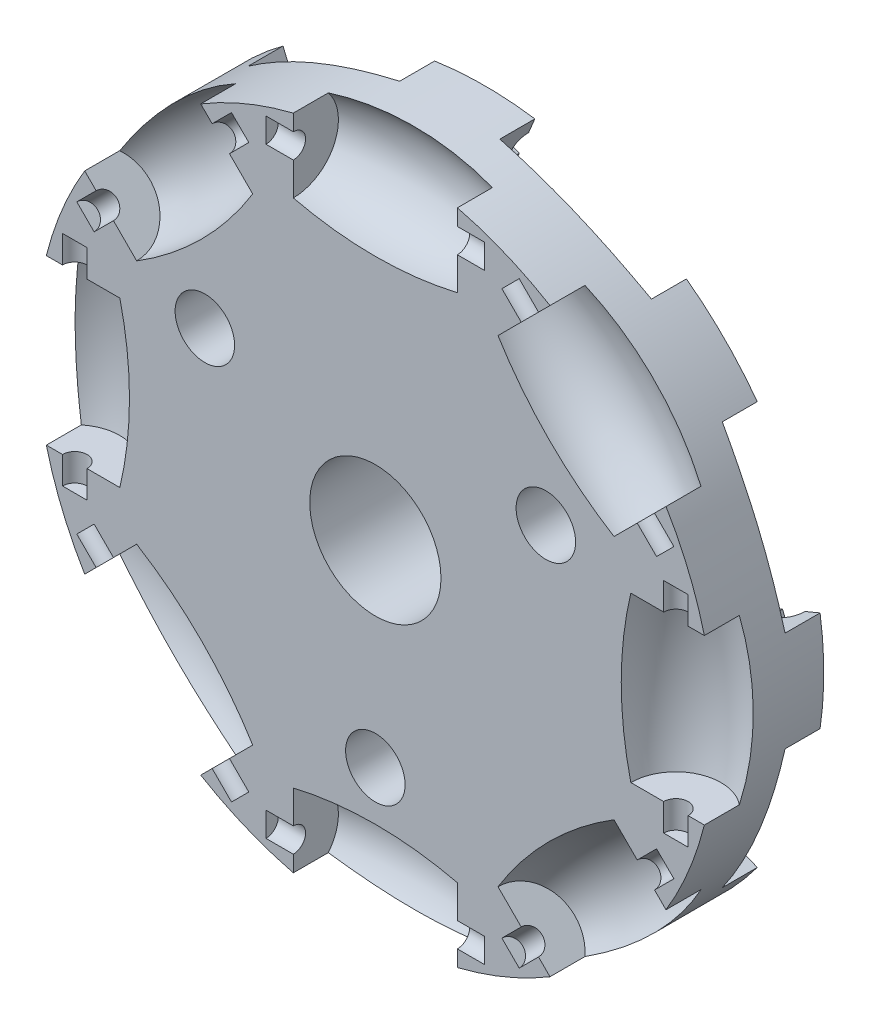
SolidWorks part; units mm, degrees
ref_plane "Front Plane" through (0, 0, 0) normal (0, 0, 1) x (1, 0, 0)
ref_plane "Top Plane" through (0, 0, 0) normal (0, 1, 0) x (1, 0, 0)
ref_plane "Right Plane" through (0, 0, 0) normal (1, 0, 0) x (0, 0, -1)
sketch "Sketch1" plane through (0, 0, 0) normal (0, 0, 1) x (1, 0, 0)
  circle A0 centre (0, 0) radius 24.6062
  point P11 (0, 0)
  dimension "D1" = 49.2125
extrude "Boss-Extrude1" add sketch "Sketch1" along normal mid plane 7.9375
ref_plane "Plane1" through (0, 0, 3.9688) normal (0, 0, 1) x (1, 0, 0)
ref_plane "Plane2" through (0, 0, -3.9688) normal (0, 0, 1) x (1, 0, 0)
sketch "Sketch5" plane through (0, 0, 3.9688) normal (0, 0, 1) x (1, 0, 0)
  line L0 (-5.9531, 25.0843) -> (-5.9531, 21.8122)
  line L1 (-5.9531, 21.8122) -> (5.9531, 21.8122)
  line L2 (5.9531, 21.8122) -> (5.9531, 25.0843)
  line L3 (-5.9531, 21.8122) -> (-8.0326, 21.8122) construction
  arc A2 (-5.9531, 25.0843) -> (5.9531, 25.0843) centre (0, 0) cw
  point P2 (0, 25.781)
  point P7 (0, 21.8122)
  dimension "D1" = 11.9062
  dimension "D2" = 7.9375
  dimension "D3" = 21.8122
revolve "Cut-Revolve5" cut sketch "Sketch5" angle 360 about L1
sketch "Sketch8" plane through (0, 0, -3.9688) normal (0, 0, 1) x (1, 0, 0)
  line L0 (4.0994, 25.453) -> (2.8472, 22.4301)
  line L1 (2.8472, 22.4301) -> (13.8472, 17.8737)
  line L2 (13.8472, 17.8737) -> (15.0993, 20.8967)
  line L3 (2.8472, 22.4301) -> (-2.3537, 24.5843) construction
  line L4 (0, 0) -> (9.4164, 22.7332) construction
  line L5 (0, 0) -> (0, 7.8748) construction
  arc A0 (4.0994, 25.453) -> (15.0993, 20.8967) centre (0, 0) cw
  arc A2 (-5.9531, 23.8753) -> (5.9531, 23.8753) centre (0, 0) ccw construction
  point P6 (8.3472, 20.1519)
  point P14 (9.866, 23.8185)
  dimension "D1" = 11.9062
  dimension "D2" = 7.9375
  dimension "D3" = 22.5
  dimension "D4" = 21.8122
revolve "Cut-Revolve6" cut sketch "Sketch8" angle 360 about L3
sketch "Sketch6" plane through (0, 0, 0) normal (1, 0, 0) x (0, 0, -1)
  arc A0 (-3.9688, 18.5402) -> (-1.429, 23.8753) centre (-3.9688, 21.8122) ccw construction
  circle A1 centre (-3.9688, 21.8122) radius 0.889
  point P4 (-3.9688, 21.8122)
  dimension "D1" = 1.778
extrude "Cut-Extrude2" cut sketch "Sketch6" against normal mid plane 15.875
ref_axis "Axis1" through (0, 0, -8.8615) along (0, 0, 1)
ref_plane "Plane3" through (0, 0, 0) normal (0.9239, -0.3827, 0) x (0, 0, -1)
sketch "Sketch10" plane through (0, 0, 0) normal (0.9239, -0.3827, 0) x (0, 0, -1)
  arc A1 (1.429, 23.8753) -> (3.9688, 18.5402) centre (3.9688, 21.8123) ccw construction
  circle A2 centre (3.9688, 21.8123) radius 0.889
  point P4 (3.9688, 21.8123)
  dimension "D1" = 1.778
extrude "Cut-Extrude3" cut sketch "Sketch10" against normal mid plane 15.875
pattern_circular "CirPattern1" count 8 over 360 about axis through (0, 0, 3.9688) along (0, 0, -1) of "Cut-Revolve5", "Cut-Revolve6", "Cut-Extrude2", "Cut-Extrude3"
sketch "Sketch16" plane through (0, 0, 3.9688) normal (0, 0, 1) x (1, 0, 0)
  circle A0 centre (0, -14.2875) radius 2.159
  circle A1 centre (-12.3733, 7.1437) radius 2.159
  circle A2 centre (12.3733, 7.1438) radius 2.159
  point P9 (0, 0)
  dimension "D1" = 4.318
  dimension "D2" = 14.2875
  dimension "D3" = 3
extrude "Cut-Extrude7" cut sketch "Sketch16" against normal through all
sketch "Sketch17" plane through (0, 0, 3.9688) normal (0, 0, 1) x (1, 0, 0)
  circle A0 centre (0, 0) radius 4.7625
  dimension "D1" = 9.525
extrude "Cut-Extrude8" cut sketch "Sketch17" against normal through all
